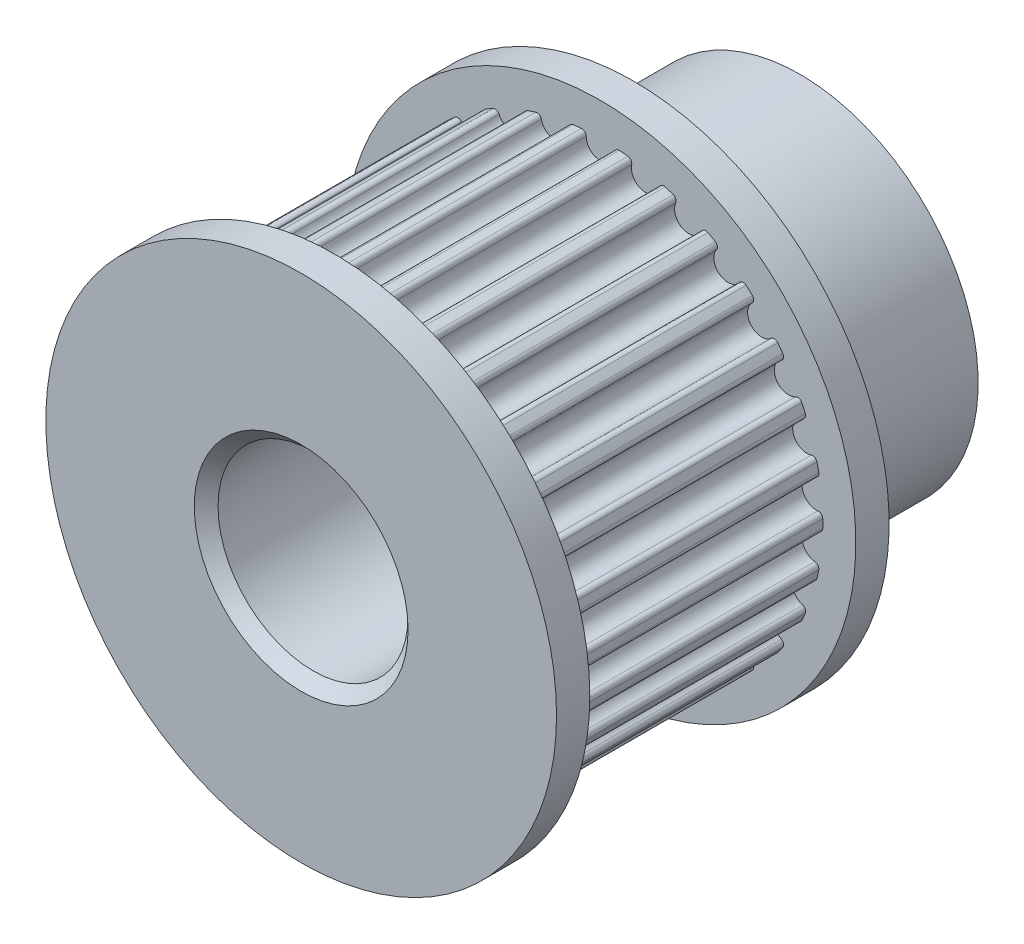
SolidWorks part; units mm, degrees
ref_plane "Front Plane" through (0, 0, 0) normal (0, 0, 1) x (1, 0, 0)
ref_plane "Top Plane" through (0, 0, 0) normal (0, 1, 0) x (1, 0, 0)
ref_plane "Right Plane" through (0, 0, 0) normal (1, 0, 0) x (0, 0, -1)
ref_axis "Axis1" through (0, 0, 55) along (0, 0, -1)
sketch "SketchRevolveGearBelt01" plane through (0, 0, 0) normal (1, 0, 0) x (0, 0, -1)
  line L0 (0, 0) -> (1, 0) construction
  line L1 (5.6, 0) -> (5.6, 9.3588)
  line L2 (5.6, 9.3588) -> (-5.6, 9.3588)
  line L3 (-5.6, 9.3588) -> (-5.6, 0)
  line L4 (-5.6, 0) -> (5.6, 0)
  dimension "GearBeltSide1" = 5.6
  dimension "GearBeltOutsideDiameter" = 9.3588
  dimension "GearBeltSide2" = 5.6
revolve "GearBelt01" add sketch "SketchRevolveGearBelt01" angle 360 about L0
sketch "SketchToothGearBelt01" plane through (0, 0, 0) normal (0, 0, 1) x (1, 0, 0)
  line L0 (-0.8012, 9.3244) -> (0, 11.8988)
  line L1 (0, 11.8988) -> (0.8012, 9.3244)
  arc A0 (0.8012, 9.3244) -> (0.6, 9.1398) centre (0.7853, 9.1398) ccw
  arc A1 (0.6, 9.1398) -> (-0.6, 9.1398) centre (0, 9.1398) cw
  arc A2 (-0.6, 9.1398) -> (-0.8012, 9.3244) centre (-0.7853, 9.1398) ccw
  dimension "GearBeltToothR1" = 0.3706
  dimension "GearBeltToothR2" = 1.2
  dimension "GearBeltToothCapX1" = 0.8012
  dimension "GearBeltToothCapY1" = 2.5744
  dimension "GearBeltToothCapX2" = 0.8012
  dimension "GearBeltToothCapY2" = 2.5744
extrude "ToothExtrudeCutGearBelt01" cut sketch "SketchToothGearBelt01" against normal blind 5.6 and the other way blind 5.6
ref_axis "Axis2" through (10.2947, 0, 0) along (-1, 0, 0)
ref_plane "Plane1" through (0, 0, 0) normal (0, 0, -1) x (1, 0, 0)
pattern_circular "PatternGearBelt01" count 30 every 12 about axis through (0, 0, 55) along (0, 0, -1) of "ToothExtrudeCutGearBelt01"
sketch "Sketch5" plane through (0, 0, 5.6) normal (0, 0, 1) x (1, 0, 0)
  circle A0 centre (0, 0) radius 10.75
extrude "Boss-Extrude1" add sketch "Sketch5" along normal blind 1.4
sketch "Sketch6" plane through (0, 0, -5.6) normal (0, 0, -1) x (-1, 0, 0)
  circle A0 centre (0, 0) radius 10.75
extrude "Boss-Extrude2" add sketch "Sketch6" along normal blind 1.4
sketch "Sketch7" plane through (0, 0, -7) normal (0, 0, -1) x (-1, 0, 0)
  circle A0 centre (0, 0) radius 7.5
extrude "Boss-Extrude3" add sketch "Sketch7" along normal blind 7
sketch "Sketch8" plane through (0, 0, -14) normal (0, 0, -1) x (-1, 0, 0)
  circle A0 centre (0, 0) radius 4
extrude "Cut-Extrude2" cut sketch "Sketch8" against normal through all
chamfer "Chamfer1" distance 0.5 angle 45 2 edges at (-4, 0, -14) (-4, 0, 7)
